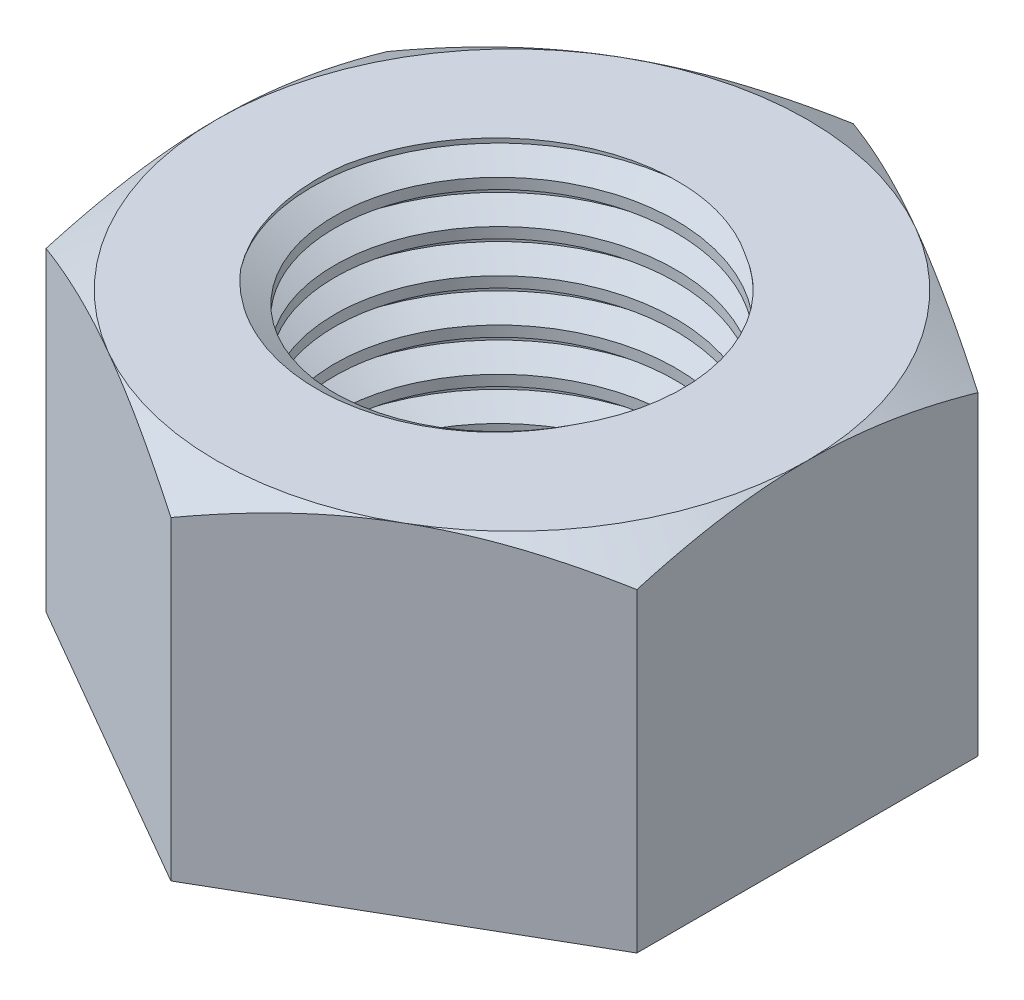
SolidWorks part; units mm, degrees
ref_plane "Front Plane" through (0, 0, 0) normal (0, 0, 1) x (1, 0, 0)
ref_plane "Top Plane" through (0, 0, 0) normal (0, 1, 0) x (1, 0, 0)
ref_plane "Right Plane" through (0, 0, 0) normal (1, 0, 0) x (0, 0, -1)
sketch "Sketch1" plane through (0, 0, 0) normal (0, 1, 0) x (1, 0, 0)
  line L1 (0, -24) -> (20.7846, -12)
  line L2 (20.7846, -12) -> (20.7846, 12)
  line L3 (20.7846, 12) -> (0, 24)
  line L4 (0, 24) -> (-20.7846, 12)
  line L5 (-20.7846, 12) -> (-20.7846, -12)
  line L6 (-20.7846, -12) -> (0, -24)
  circle A0 centre (0, 0) radius 20.7846 construction
  dimension "D1" = 48
extrude "Boss-Extrude1" add sketch "Sketch1" along normal blind 24
hole_wizard "Ø1.0mm Dowel Hole2" positions "Sketch5" profile "Sketch6" hole size "Ø1.0" standard "ANSI Metric" end condition through all
sketch "Sketch5" plane through (0, 24, 0) normal (0, 1, 0) x (1, 0, 0)
  point P0 (0, 0)
sketch "Sketch6" plane through (0, 24, 0) normal (1, 0, 0) x (0, 0, 1)
  line L0 (0, 0) -> (0, 24)
  line L1 (0, 24) -> (12, 24)
  line L2 (12, 24) -> (12, 0)
  line L5 (12, 0) -> (0, 0)
  line L11 (0, -6.35) -> (0, 107.95) construction
  dimension "Thru Hole Dia." = 24
  dimension "Thru Hole Depth" = 24
thread "Thread1" pitch 3 method cut profile "Thread Profile1" start angle 0, offset 10, length 40, pitch 3, diameter 24
ref_plane "Plane1" through (-12, 34, 0) normal (0, 0, 1) x (-1, 0, 0)
sketch "Thread Profile1" plane through (-12, 34, 0) normal (0, 0, 1) x (-1, 0, 0)
  line L0 (0, 0) -> (0, 3) construction
  line L1 (0, 0) -> (1.6238, 0.9375)
  line L2 (1.6238, 0.9375) -> (1.6238, 1.3125)
  line L3 (1.6238, 1.3125) -> (0, 2.25)
  line L4 (1.6238, 1.125) -> (0, 1.125) construction
  line L11 (0, 0) -> (0, 2.25)
  point P2 (0, 0)
  dimension "Pitch" = 3
  dimension "Profile_Angle" = 60
  dimension "Profile_Land" = 0.375
  dimension "Profile_Height" = 1.6238
sketch "Sketch12" plane through (0, 24, 0) normal (0, 1, 0) x (1, 0, 0)
  circle A0 centre (0, 0) radius 20.7846
ref_plane "Plane2" through (0, 0, 0) normal (0.5, 0, 0.866) x (0.866, 0, -0.5)
sketch "Sketch13" plane through (0, 0, 0) normal (0.5, 0, 0.866) x (0.866, 0, -0.5)
  line L0 (20.7846, 24) -> (-20.7846, 24) construction
  line L1 (20.7846, 24) -> (-20.7846, 24) construction
  line L5 (0, 24) -> (0, -5.5611) construction
  line L6 (20.7846, 24) -> (32.4126, 24)
  line L7 (32.4126, 24) -> (32.4126, 17.2865)
  line L8 (32.4126, 17.2865) -> (20.7846, 24)
  dimension "D1" = 30
revolve "Cut-Revolve1" cut sketch "Sketch13" angle 360 about L5
